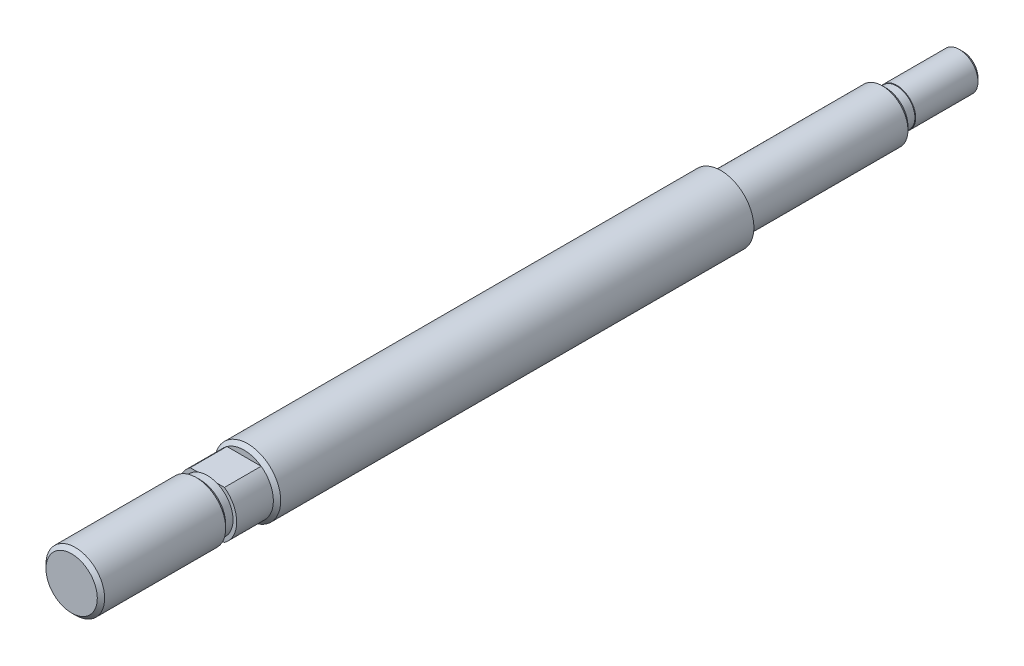
SolidWorks part; units mm, degrees
ref_plane "Front Plane" through (0, 0, 0) normal (0, 0, 1) x (1, 0, 0)
ref_plane "Top Plane" through (0, 0, 0) normal (0, 1, 0) x (1, 0, 0)
ref_plane "Right Plane" through (0, 0, 0) normal (1, 0, 0) x (0, 0, -1)
sketch "Sketch1" plane through (0, 0, 0) normal (0, 0, 1) x (1, 0, 0)
  circle A0 centre (0, 0) radius 9
  dimension "D1" = 18
extrude "Boss-Extrude1" add sketch "Sketch1" along normal mid plane 243
sketch "Sketch2" plane through (0, 0, -121.5) normal (0, 0, -1) x (-1, 0, 0)
  circle A0 centre (0, 0) radius 5.1
  dimension "D1" = 10.2
extrude "Cut-Extrude2" cut sketch "Sketch2" against normal blind 19 flip side to cut
cosmetic thread "Cosmetic Thread1" parameters "D2"=10.072
sketch "Sketch3" plane through (0, 0, -102.5) normal (0, 0, -1) x (-1, 0, 0)
  circle A0 centre (0, 0) radius 5
  dimension "D1" = 10
extrude "Cut-Extrude3" cut sketch "Sketch3" against normal blind 2 flip side to cut
sketch "Sketch4" plane through (0, 0, -100.5) normal (0, 0, -1) x (-1, 0, 0)
  circle A0 centre (0, 0) radius 7
  dimension "D1" = 14
extrude "Cut-Extrude4" cut sketch "Sketch4" against normal blind 45 flip side to cut
chamfer "Chamfer1" distance 1 angle 45 3 edges at (-7, 0, -100.5) (-5.1, 0, -102.5) (-5.1, 0, -121.5)
sketch "Sketch5" plane through (0, 0, 121.5) normal (0, 0, 1) x (1, 0, 0)
  circle A0 centre (0, 0) radius 6.5
  dimension "D1" = 13
extrude "Cut-Extrude5" cut sketch "Sketch5" against normal blind 47 flip side to cut
sketch "Sketch6" plane through (0, 0, 74.5) normal (0, 0, 1) x (1, 0, 0)
  circle A0 centre (0, 0) radius 8
  dimension "D1" = 16
extrude "Boss-Extrude2" add sketch "Sketch6" along normal blind 10
sketch "Sketch8" plane through (0, 0, 121.5) normal (0, 0, 1) x (1, 0, 0)
  circle A0 centre (0, 0) radius 8
  dimension "D1" = 16
extrude "Boss-Extrude3" add sketch "Sketch8" against normal blind 35
cosmetic thread "Cosmetic Thread3" parameters "D2"=13.797
chamfer "Chamfer3" distance 1 angle 45 3 edges at (9, 0, 74.5) (8, 0, 86.5) (8, 0, 121.5)
sketch "Sketch12" plane through (0, 0, 86.5) normal (0, 0, -1) x (-1, 0, 0)
  circle A0 centre (0, 0) radius 7
extrude "Boss-Extrude4" add sketch "Sketch12" along normal up to next
sketch "Sketch14" plane through (0, 0, 0) normal (1, 0, 0) x (0, 0, -1)
  line L0 (-74.5, 0) -> (-84.5, 0) construction
  line L1 (-74.5, 8) -> (-74.5, -8) construction
  line L2 (-84.5, 7) -> (-84.5, -7) construction
  line L3 (-84.5, 6.5) -> (-84.5, 8)
  line L4 (-84.5, 8) -> (-84.5, -8) construction
  line L5 (-84.5, 6.5) -> (-74.5, 6.5)
  line L6 (-84.5, 8) -> (-74.5, 8)
  line L7 (-84.5, -6.5) -> (-74.5, -6.5)
  line L8 (-74.5, 8) -> (-74.5, 6.5)
  line L9 (-84.5, -6.5) -> (-84.5, -8)
  line L10 (-84.5, -8) -> (-74.5, -8)
  line L11 (-74.5, -8) -> (-74.5, -6.5)
  dimension "D1" = 6.5
extrude "Cut-Extrude7" cut sketch "Sketch14" against normal mid plane 35
